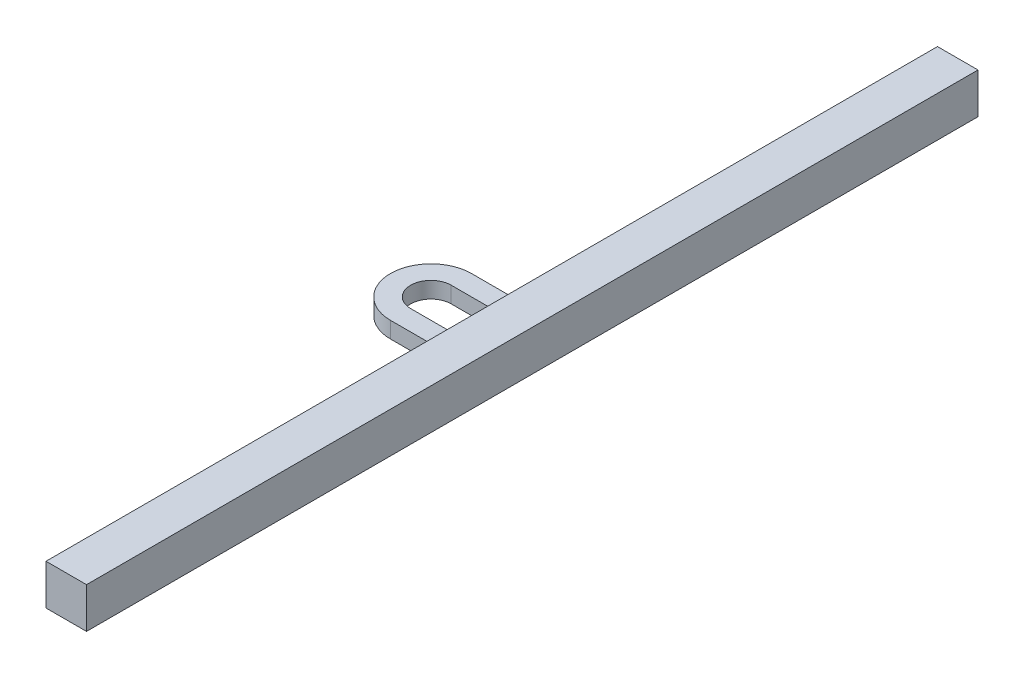
SolidWorks part; units mm, degrees
material "Alloy Steel"
ref_plane "Front Plane" through (0, 0, 0) normal (0, 0, 1) x (1, 0, 0)
ref_plane "Top Plane" through (0, 0, 0) normal (0, 1, 0) x (1, 0, 0)
ref_plane "Right Plane" through (0, 0, 0) normal (1, 0, 0) x (0, 0, -1)
sketch "Sketch1" plane through (0, 0, 0) normal (0, 1, 0) x (1, 0, 0)
  line L0 (0, 0) -> (-25.4, 0) construction
  line L1 (-6.35, -139.7) -> (6.35, -139.7)
  line L2 (-6.35, -139.7) -> (-6.35, 139.7)
  line L3 (-6.35, 139.7) -> (6.35, 139.7)
  line L4 (6.35, -139.7) -> (6.35, 139.7)
  line L5 (-6.35, -139.7) -> (6.35, 139.7) construction
  line L6 (-6.35, 139.7) -> (6.35, -139.7) construction
  line L7 (-25.4, 6.35) -> (-6.35, 6.35)
  line L8 (-25.4, -6.35) -> (-6.35, -6.35)
  line L9 (-25.4, 12.7) -> (-6.35, 12.7)
  line L10 (-25.4, -12.7) -> (-6.35, -12.7)
  circle A0 centre (-25.4, 0) radius 6.35
  circle A1 centre (-25.4, 0) radius 12.7
  point P0 (0, 0)
  dimension "D4" = 12.7
  dimension "D5" = 25.4
  dimension "D1" = 279.4
  dimension "D2" = 12.7
  dimension "D3" = 25.4
extrude "Boss-Extrude1" add sketch "Sketch1" along normal blind 12.7 contours L1 L4 L3 L2 region at (0, 0, 0)
extrude "Boss-Extrude2" add sketch "Sketch1<4>" along normal blind 5.08 contours A1 L7 L2 L9 | A1 L8 A0 L7 | A1 L10 L2 L8 region at (-12.2577, 0, 9.9211) region at (-37.7526, 0, 0) region at (-12.2577, 0, -9.9211)
sketch "Sketch1<4>" plane through (0, 0, 0) normal (0, 1, 0) x (1, 0, 0) same geometry as "Sketch1"
